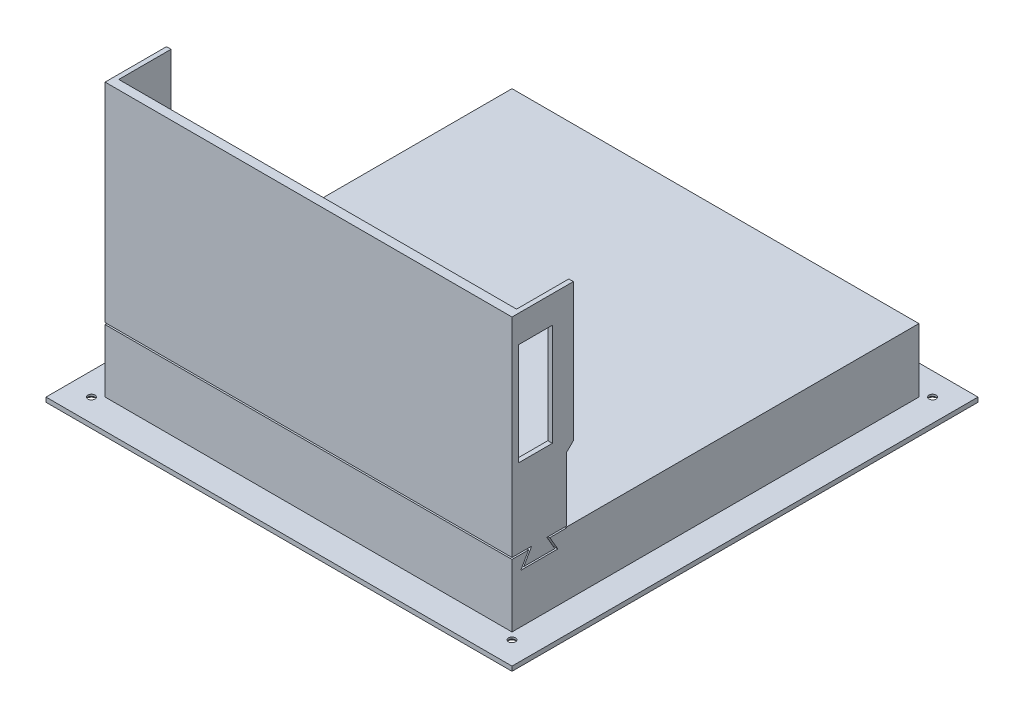
SolidWorks part; units mm, degrees
ref_plane "Front Plane" through (0, 0, 0) normal (0, 0, 1) x (1, 0, 0)
ref_plane "Top Plane" through (0, 0, 0) normal (0, 1, 0) x (1, 0, 0)
ref_plane "Right Plane" through (0, 0, 0) normal (1, 0, 0) x (0, 0, -1)
sketch "Sketch1" plane through (0, 0, 0) normal (0, 1, 0) x (1, 0, 0)
  line L1 (-87.5, 87.5) -> (87.5, 87.5)
  line L2 (-87.5, 87.5) -> (-87.5, -87.5)
  line L3 (-87.5, -87.5) -> (87.5, -87.5)
  line L4 (87.5, 87.5) -> (87.5, -87.5)
  line L5 (-87.5, 87.5) -> (87.5, -87.5) construction
  line L6 (-87.5, -87.5) -> (87.5, 87.5) construction
  point P0 (0, 0)
  dimension "D1" = 175
  dimension "D2" = 175
extrude "Boss-Extrude1" add sketch "Sketch1" along normal blind 2
sketch "Sketch2" plane through (0, 0, 0) normal (0, 1, 0) x (1, 0, 0)
  line L4 (-83, -33.5) -> (-79.25, -33.5)
  line L5 (-71.125, -48.5) -> (-61.125, -48.5)
  line L6 (-82.5, 42.5) -> (-78.75, 42.5)
  line L7 (-82.5, 42.5) -> (-82.5, 30.5)
  line L8 (-82.5, 30.5) -> (-78.75, 30.5)
  line L9 (-78.75, 42.5) -> (-78.75, 30.5)
  line L10 (-82.5, 42.5) -> (-78.75, 30.5) construction
  line L11 (-82.5, 30.5) -> (-78.75, 42.5) construction
  line L12 (87.5, 87.5) -> (-87.5, 87.5) construction
  line L13 (-87.5, 87.5) -> (-87.5, -87.5) construction
  line L14 (-48.7483, 30.5) -> (-52.4983, 30.5)
  line L15 (-48.7483, 42.5) -> (-48.7483, 30.5)
  line L16 (-52.4983, 42.5) -> (-52.4983, 30.5)
  line L17 (-48.7483, 42.5) -> (-52.4983, 42.5)
  line L18 (-44.5, 49) -> (-40.75, 49)
  line L19 (-83, -33.5) -> (-83, -45.5)
  line L20 (-83, -45.5) -> (-79.25, -45.5)
  line L21 (-79.25, -33.5) -> (-79.25, -45.5)
  line L22 (-83, -33.5) -> (-79.25, -45.5) construction
  line L23 (-83, -45.5) -> (-79.25, -33.5) construction
  line L28 (-87.5, -87.5) -> (87.5, -87.5) construction
  line L29 (-53, -33.5) -> (-49.25, -33.5)
  line L30 (-53, -33.5) -> (-53, -45.5)
  line L31 (-53, -45.5) -> (-49.25, -45.5)
  line L32 (-49.25, -33.5) -> (-49.25, -45.5)
  line L33 (-53, -33.5) -> (-49.25, -45.5) construction
  line L34 (-53, -45.5) -> (-49.25, -33.5) construction
  line L35 (-44.5, 49) -> (-44.5, 37)
  line L36 (-44.5, 37) -> (-40.75, 37)
  line L37 (-40.75, 49) -> (-40.75, 37)
  line L38 (-44.5, 49) -> (-40.75, 37) construction
  line L39 (-44.5, 37) -> (-40.75, 49) construction
  line L40 (-14.5, 49) -> (-10.75, 49)
  line L41 (-14.5, 49) -> (-14.5, 37)
  line L42 (-14.5, 37) -> (-10.75, 37)
  line L43 (-10.75, 49) -> (-10.75, 37)
  line L44 (-14.5, 49) -> (-10.75, 37) construction
  line L45 (-14.5, 37) -> (-10.75, 49) construction
  line L46 (-70.6242, 5.5249) -> (-60.6242, 5.5249)
  line L47 (-70.6242, 75.5249) -> (-60.6242, 75.5249)
  line L48 (-70.6242, 75.5249) -> (-70.6242, 67.5249)
  line L49 (-70.6242, 67.5249) -> (-60.6242, 67.5249)
  line L50 (-60.6242, 75.5249) -> (-60.6242, 67.5249)
  line L51 (-70.6242, 75.5249) -> (-60.6242, 67.5249) construction
  line L52 (-70.6242, 67.5249) -> (-60.6242, 75.5249) construction
  line L53 (-70.6242, 5.5249) -> (-70.6242, -2.4751)
  line L54 (-70.6242, -2.4751) -> (-60.6242, -2.4751)
  line L55 (-60.6242, 5.5249) -> (-60.6242, -2.4751)
  line L56 (-70.6242, 5.5249) -> (-60.6242, -2.4751) construction
  line L57 (-70.6242, -2.4751) -> (-60.6242, 5.5249) construction
  line L58 (-71.125, -20.5) -> (-61.125, -20.5)
  line L59 (-71.125, -20.5) -> (-71.125, -28.5)
  line L60 (-71.125, -28.5) -> (-61.125, -28.5)
  line L61 (-61.125, -20.5) -> (-61.125, -28.5)
  line L62 (-71.125, -20.5) -> (-61.125, -28.5) construction
  line L63 (-71.125, -28.5) -> (-61.125, -20.5) construction
  line L64 (-71.125, -48.5) -> (-71.125, -56.5)
  line L65 (-71.125, -56.5) -> (-61.125, -56.5)
  line L66 (-61.125, -48.5) -> (-61.125, -56.5)
  line L67 (-71.125, -48.5) -> (-61.125, -56.5) construction
  line L68 (-71.125, -56.5) -> (-61.125, -48.5) construction
  line L69 (-32.625, 6.5) -> (-22.625, 6.5)
  line L70 (-32.625, 76.5) -> (-22.625, 76.5)
  line L71 (-32.625, 76.5) -> (-32.625, 68.5)
  line L72 (-32.625, 68.5) -> (-22.625, 68.5)
  line L73 (-22.625, 76.5) -> (-22.625, 68.5)
  line L74 (-32.625, 76.5) -> (-22.625, 68.5) construction
  line L75 (-32.625, 68.5) -> (-22.625, 76.5) construction
  line L76 (-32.625, 6.5) -> (-32.625, -1.5)
  line L77 (-32.625, -1.5) -> (-22.625, -1.5)
  line L78 (-22.625, 6.5) -> (-22.625, -1.5)
  line L79 (-32.625, 6.5) -> (-22.625, -1.5) construction
  line L80 (-32.625, -1.5) -> (-22.625, 6.5) construction
  line L87 (4.5, 59.625) -> (12.5, 59.625)
  line L91 (4.5, 59.625) -> (4.5, 49.625)
  line L92 (4.5, 49.625) -> (12.5, 49.625)
  line L93 (12.5, 59.625) -> (12.5, 49.625)
  line L94 (4.5, 59.625) -> (12.5, 49.625) construction
  line L95 (4.5, 49.625) -> (12.5, 59.625) construction
  line L99 (87.5, -87.5) -> (87.5, 87.5) construction
  line L100 (57.5, 59.625) -> (65.5, 59.625)
  line L101 (57.5, 59.625) -> (57.5, 49.625)
  line L106 (57.5, 49.625) -> (65.5, 49.625)
  line L107 (65.5, 59.625) -> (65.5, 49.625)
  line L112 (57.5, 59.625) -> (65.5, 49.625) construction
  line L113 (57.5, 49.625) -> (65.5, 59.625) construction
  line L114 (32.5, 71.5) -> (44.5, 71.5)
  line L115 (32.5, 51.25) -> (44.5, 51.25)
  line L120 (32.5, 71.5) -> (32.5, 67.75)
  line L121 (32.5, 67.75) -> (44.5, 67.75)
  line L122 (32.5, 51.25) -> (32.5, 47.5)
  line L123 (32.5, 47.5) -> (44.5, 47.5)
  line L124 (44.5, 51.25) -> (44.5, 47.5)
  line L125 (32.5, 51.25) -> (44.5, 47.5) construction
  line L126 (32.5, 47.5) -> (44.5, 51.25) construction
  line L127 (44.5, 71.5) -> (44.5, 67.75)
  line L128 (32.5, 71.5) -> (44.5, 67.75) construction
  line L129 (32.5, 67.75) -> (44.5, 71.5) construction
  point P0 (-80.625, 36.5)
  point P5 (-52.4983, 36.5)
  point P6 (-78.75, 36.5)
  point P7 (-80.625, 42.5)
  point P16 (-81.125, -39.5)
  point P17 (-42.625, 43)
  point P19 (-53, -39.5)
  point P25 (8.5, 54.625)
  point P30 (-79.25, -39.5)
  point P31 (-65.6242, 1.5249)
  point P33 (-14.5, 43)
  point P38 (-65.6242, 71.5249)
  point P43 (-40.75, 43)
  point P51 (-27.625, 2.5)
  point P53 (-27.625, 72.5)
  point P55 (-66.125, -24.5)
  point P56 (-66.125, -52.5)
  point P75 (61.5, 54.625)
  point P80 (38.5, 49.375)
  point P85 (38.5, 69.625)
  dimension "D1" = 3.75
  dimension "D2" = 12
  dimension "D3" = 45
  dimension "D4" = 5
  dimension "D5" = 26.2517
  dimension "D6" = 3.75
  dimension "D7" = 12
  dimension "D8" = 3.75
  dimension "D9" = 12
  dimension "D10" = 4.5
  dimension "D11" = 42
  dimension "D12" = 26.25
  dimension "D13" = 26.25
  dimension "D14" = 43
  dimension "D15" = 11
  dimension "D16" = 10
  dimension "D17" = 8
  dimension "D18" = 8.1258
  dimension "D19" = 25.0249
  dimension "D20" = 62
  dimension "D21" = 8
  dimension "D22" = 20
  dimension "D23" = 10
  dimension "D24" = 8.125
  dimension "D25" = 5
  dimension "D26" = 10
  dimension "D27" = 8
  dimension "D28" = 62
  dimension "D29" = 19.5
  dimension "D30" = 8.125
  dimension "D31" = 10
  dimension "D32" = 8
  dimension "D33" = 10
  dimension "D34" = 8
  dimension "D35" = 43
  dimension "D36" = 20
  dimension "D37" = 40
  dimension "D38" = 45
  dimension "D39" = 8.125
  dimension "D40" = 3.75
  dimension "D41" = 12
  dimension "D42" = 16.5
  dimension "D43" = 3.75
  dimension "D44" = 12
extrude "Boss-Extrude13" add sketch "Sketch2" against normal blind 23 contours L87 L93 L92 L91 | L115 L124 L123 L122 | L114 L127 L121 L120 | L100 L107 L106 L101 region at (8.5, 0, -54.625) region at (38.5, 0, -49.375)
extrude "Boss-Extrude14" add sketch "Sketch2<4>" against normal blind 20 contours L5 L66 L65 L64 | L4 L21 L20 L19 | L29 L32 L31 L30 | L58 L61 L60 L59 region at (-81.125, 0, 39.5) region at (-66.125, 0, 52.5) region at (-51.125, 0, 39.5)
sketch "Sketch2<4>" plane through (0, 0, 0) normal (0, 1, 0) x (1, 0, 0) same geometry as "Sketch2"
extrude "Boss-Extrude15" add sketch "Sketch2<5>" against normal blind 22 contours L69 L78 L77 L76 | L35 L36 L37 L18 | L70 L73 L72 L71 | L40 L43 L42 L41 region at (-27.625, 0, -2.5)
sketch "Sketch2<5>" plane through (0, 0, 0) normal (0, 1, 0) x (1, 0, 0) same geometry as "Sketch2"
extrude "Boss-Extrude19" add sketch "Sketch2<7>" against normal blind 22 contours L46 L55 L54 L53 | L17 L15 L14 L16 | L7 L8 L9 L6 | L47 L50 L49 L48 region at (-50.6233, 0, -36.5) region at (-65.6242, 0, -1.5249)
sketch "Sketch2<7>" plane through (0, 0, 0) normal (0, 1, 0) x (1, 0, 0) same geometry as "Sketch2"
extrude "Boss-Extrude20" add sketch "Sketch2<8>" against normal blind 5 contours L70 L73 L72 L71 | L40 L43 L42 L41 | L18 L37 L36 L35 | L78 L77 L76 L69
sketch "Sketch2<8>" plane through (0, 0, 0) normal (0, 1, 0) x (1, 0, 0) same geometry as "Sketch2"
sketch "Sketch11" plane through (0, 0, 0) normal (0, -1, 0) x (1, 0, 0)
  line L0 (19.5, -10.5) -> (-0.5, -10.5)
  line L1 (79.5, -10.5) -> (24.5, -10.5)
  line L2 (79.5, -10.5) -> (79.5, -5.5)
  line L3 (79.5, -5.5) -> (24.5, -5.5)
  line L4 (-0.5, -10.5) -> (-0.5, -5.5)
  line L5 (24.5, -30.5) -> (19.5, -30.5)
  line L6 (24.5, -30.5) -> (24.5, -10.5)
  line L7 (24.5, 1.5) -> (19.5, 1.5)
  line L8 (19.5, -30.5) -> (19.5, -10.5)
  line L9 (19.5, -5.5) -> (19.5, 1.5)
  line L10 (19.5, -5.5) -> (-0.5, -5.5)
  line L12 (87.5, 87.5) -> (87.5, -87.5) construction
  line L13 (87.5, -87.5) -> (-87.5, -87.5) construction
  line L14 (24.5, -5.5) -> (24.5, 1.5)
  dimension "D1" = 5
  dimension "D2" = 5
  dimension "D3" = 8
  dimension "D4" = 57
  dimension "D6" = 20
  dimension "D7" = 55
extrude "Boss-Extrude7" add sketch "Sketch11" along normal blind 33
sketch "Sketch10" plane through (0, 0, 0) normal (0, -1, 0) x (1, 0, 0)
  line L0 (10.5, 35.5) -> (-21.5, 35.5)
  line L1 (72.5, 35.5) -> (17.5, 35.5)
  line L2 (72.5, 35.5) -> (72.5, 45.5)
  line L3 (72.5, 45.5) -> (17.5, 45.5)
  line L4 (-21.5, 35.5) -> (-21.5, 45.5)
  line L5 (17.5, 12.5) -> (10.5, 12.5)
  line L6 (17.5, 12.5) -> (17.5, 35.5)
  line L7 (17.5, 65.5) -> (10.5, 65.5)
  line L8 (10.5, 12.5) -> (10.5, 35.5)
  line L9 (17.5, 45.5) -> (17.5, 65.5)
  line L10 (10.5, 45.5) -> (10.5, 65.5)
  line L11 (10.5, 45.5) -> (-21.5, 45.5)
  line L12 (87.5, 87.5) -> (87.5, -87.5) construction
  line L13 (87.5, -87.5) -> (-87.5, -87.5) construction
  dimension "D1" = 7
  dimension "D2" = 10
  dimension "D3" = 100
  dimension "D4" = 20
  dimension "D6" = 55
  dimension "D7" = 15
  dimension "D8" = 23
extrude "Boss-Extrude6" add sketch "Sketch10" along normal blind 30
sketch "Sketch4" plane through (0, 2, 0) normal (0, -1, 0) x (1, 0, 0)
  line L0 (-87.5, 87.5) -> (87.5, 87.5) construction
  line L1 (-89.5, 89.5) -> (89.5, 89.5)
  line L3 (-87.5, 87.5) -> (87.5, 87.5)
  line L6 (89.5, 89.5) -> (89.5, -89.5)
  line L8 (87.5, 87.5) -> (87.5, -87.5)
  line L10 (-89.5, 89.5) -> (-89.5, -89.5)
  line L12 (-87.5, 87.5) -> (-87.5, -87.5)
  line L13 (-89.5, -89.5) -> (89.5, -89.5)
  line L15 (-87.5, -87.5) -> (87.5, -87.5)
  line L17 (87.5, 87.5) -> (87.5, -87.5) construction
  line L21 (-87.5, -87.5) -> (-87.5, 87.5) construction
  line L22 (87.5, -87.5) -> (-87.5, -87.5) construction
  dimension "D2" = 2
  dimension "D3" = 2
  dimension "D5" = 2
  dimension "D6" = 2
extrude "Boss-Extrude3" add sketch "Sketch4" along normal blind 30
sketch "Sketch5" plane through (0, -28, 0) normal (0, -1, 0) x (1, 0, 0)
  line L1 (-102.5, 102.5) -> (102.5, 102.5)
  line L2 (-102.5, 102.5) -> (-102.5, -102.5)
  line L3 (-102.5, -102.5) -> (102.5, -102.5)
  line L4 (102.5, 102.5) -> (102.5, -102.5)
  line L5 (-102.5, 102.5) -> (102.5, -102.5) construction
  line L6 (-102.5, -102.5) -> (102.5, 102.5) construction
  line L7 (-89.5, 89.5) -> (89.5, 89.5)
  line L8 (-89.5, 89.5) -> (-89.5, -89.5)
  line L9 (-89.5, -89.5) -> (89.5, -89.5)
  line L10 (89.5, 89.5) -> (89.5, -89.5)
  line L11 (-89.5, 89.5) -> (89.5, -89.5) construction
  line L12 (-89.5, -89.5) -> (89.5, 89.5) construction
  point P0 (0, 0)
  point P6 (0, 0)
  dimension "D1" = 205
  dimension "D2" = 205
sketch "Sketch15" plane through (0, 2, 0) normal (0, 1, 0) x (1, 0, 0)
  line L0 (89.5, 89.5) -> (89.5, -89.5) construction
  line L1 (-89.5, -89.5) -> (89.5, -89.5)
  line L2 (-89.5, -89.5) -> (-89.5, -87.5)
  line L3 (-89.5, -87.5) -> (89.5, -87.5)
  line L4 (89.5, -89.5) -> (89.5, -87.5)
  dimension "D1" = 2
extrude "Boss-Extrude9" add sketch "Sketch15" along normal blind 90
sketch "Sketch13" plane through (0, 0, 0) normal (0, -1, 0) x (1, 0, 0)
  line L5 (87.5, 87.5) -> (87.5, -87.5) construction
  line L16 (-87.5, 87.5) -> (87.5, 87.5)
  line L17 (-87.5, 87.5) -> (-87.5, 67.5)
  line L18 (-87.5, 67.5) -> (87.5, 67.5)
  line L19 (87.5, 87.5) -> (87.5, 67.5)
  dimension "D1" = 20
extrude "Cut-Extrude2" cut sketch "Sketch13" against normal up to surface (2 mm away) up to face at (0, 2, -1)
sketch "Sketch17" plane through (0, 0, 87.5) normal (0, 0, -1) x (-1, 0, 0)
  line L12 (0.5, 35) -> (15.5, 35)
  line L14 (15.5, 50) -> (20.5, 50)
  line L16 (20.5, 30) -> (0.5, 30)
  line L17 (0.5, 30) -> (0.5, 35)
  line L19 (-87.5, 35) -> (-62.5, 35)
  line L20 (-62.5, 35) -> (-62.5, 30)
  line L21 (-62.5, 30) -> (-87.5, 30)
  line L22 (-87.5, 30) -> (-87.5, 35)
  line L24 (15.5, 50) -> (15.5, 35)
  line L25 (-89.5, 92) -> (-89.5, 2) construction
  line L29 (13.5, 77.3) -> (18.5, 77.3)
  line L30 (13.5, 77.3) -> (13.5, 90)
  line L31 (13.5, 90) -> (18.5, 90)
  line L32 (18.5, 77.3) -> (18.5, 90)
  line L33 (56.5, 35) -> (56.5, 15)
  line L34 (56.5, 35) -> (20.5, 35)
  line L36 (51.5, 30) -> (20.5, 30)
  line L38 (56.5, 15) -> (87.5, 15)
  line L39 (87.5, 15) -> (87.5, 10)
  line L40 (87.5, 10) -> (51.5, 10)
  line L41 (51.5, 10) -> (51.5, 30)
  line L43 (20.5, 35) -> (20.5, 50)
  line L45 (-89.5, 92) -> (89.5, 92) construction
  line L46 (89.5, 92) -> (89.5, 2) construction
  point P6 (-62.5, 32.5)
  point P26 (0.5, 32.5)
  dimension "D3" = 5
  dimension "D4" = 20
  dimension "D5" = 5
  dimension "D6" = 20
  dimension "D7" = 5
  dimension "D8" = 12.7
  dimension "D10" = 2
  dimension "D11" = 15
  dimension "D12" = 5
  dimension "D13" = 25
  dimension "D14" = 31
  dimension "D15" = 2
  dimension "D16" = 2
  dimension "D17" = 2
  dimension "D18" = 5
  dimension "D19" = 36
  dimension "D20" = 63
  dimension "D21" = 5
  dimension "D22" = 20
  dimension "D23" = 20
  dimension "D24" = 27.3
extrude "Boss-Extrude11" add sketch "Sketch17" along normal blind 5 contours L22 L21 L20 L19 | L16 L43 L14 L24 L12 L17 | L29 L32 L31 L30 | L34 L43 L14 L24 L12 L17 L16 L36 L41 L40 L39 L38 L33 region at (-8, 34.0425, 87.5) region at (75, 32.5, 87.5) region at (-16, 83.65, 87.5)
ref_plane "Plane1" through (87.5, 2, 87.5) normal (0, 0, 1) x (1, 0, 0)
sketch "Sketch24" plane through (89.5, 0, 0) normal (1, 0, 0) x (0, 0, -1)
  line L0 (-65.5, 2) -> (-65.5, 30.4086)
  line L1 (89.5, 2) -> (-87.5, 2) construction
  line L2 (-65.5, 30.4086) -> (-62.5, 33.4086)
  line L3 (-62.5, 33.4086) -> (-62.5, 92)
  line L4 (-62.5, 92) -> (-87.5, 92)
  line L5 (-87.5, 92) -> (-87.5, 2) construction
  line L6 (-87.5, 92) -> (-87.5, 2)
  line L7 (-87.5, 2) -> (-65.5, 2)
  dimension "D1" = 225
  dimension "D2" = 22
  dimension "D3" = 25
  dimension "D4" = 58.5914
extrude "Boss-Extrude16" add sketch "Sketch24" against normal blind 2 separate body
sketch "Sketch26" plane through (-89.5, 0, 0) normal (-1, 0, 0) x (0, 0, 1)
  line L0 (65.5, 2) -> (65.5, 30.4086)
  line L1 (65.5, 30.4086) -> (62.5, 33.4086)
  line L2 (62.5, 33.4086) -> (62.5, 92)
  line L3 (62.5, 92) -> (87.5, 92)
  line L4 (87.5, 92) -> (87.5, 2)
  line L5 (87.5, 2) -> (65.5, 2)
extrude "Boss-Extrude17" add sketch "Sketch26" against normal blind 2
sketch "Sketch27" plane through (-87.5, 0, 0) normal (1, 0, 0) x (0, 0, -1)
  line L0 (-64.5, 34.237) -> (-67.5, 31.237)
  line L1 (-62.5, 92) -> (-64.5, 92)
  line L2 (-62.5, 92) -> (-62.5, 33.4086)
  line L4 (-64.5, 92) -> (-64.5, 34.237)
  line L5 (-67.5, 31.237) -> (-67.5, 2)
  line L6 (-67.5, 2) -> (-65.5, 2)
  line L7 (-65.5, 2) -> (-65.5, 30.4086)
  line L8 (-65.5, 30.4086) -> (-62.5, 33.4086)
  line L9 (-87.5, 2) -> (-65.5, 2) construction
  line L10 (-65.5, 30.4086) -> (-65.5, 2) construction
  dimension "D1" = 2
  dimension "D2" = 2
  dimension "D3" = 2
extrude "Boss-Extrude18" add sketch "Sketch27" along normal up to next
extrude "Boss-Extrude4" add sketch "Sketch5" against normal blind 2
sketch "Sketch8" plane through (0, -28, 0) normal (0, -1, 0) x (-1, 0, 0)
  line L0 (102.5, 102.5) -> (-102.5, 102.5) construction
  line L1 (-102.5, 102.5) -> (-102.5, -102.5) construction
  line L2 (102.5, -102.5) -> (102.5, 102.5) construction
  line L3 (-102.5, -102.5) -> (102.5, -102.5) construction
  point P0 (-92.5, 92.5)
  point P2 (92.5, 92.5)
  point P4 (92.5, -92.5)
  point P6 (-92.5, -92.5)
  dimension "D1" = 10
  dimension "D2" = 10
  dimension "D3" = 10
  dimension "D4" = 10
  dimension "D5" = 10
  dimension "D6" = 10
  dimension "D7" = 10
  dimension "D8" = 10
hole_wizard "CSK for M2.5 Flat Head Machine Screw1" positions "Sketch8" profile "Sketch7" countersink size "M2.5" standard "ANSI Metric" end condition up to next
sketch "Sketch7" plane through (92.5, -28, -92.5) normal (1, 0, 0) x (0, 0, -1)
  line L0 (0, 0) -> (0, 2)
  line L1 (0, 2) -> (1.55, 2)
  line L2 (1.55, 2) -> (1.55, 1.2)
  line L3 (1.55, 1.2) -> (2.75, 0)
  line L5 (2.75, 0) -> (0, 0)
  line L6 (-1.55, 1.2) -> (-2.75, 0) construction
  line L11 (0, -6.35) -> (0, 107.95) construction
  dimension "Thru Hole Dia." = 3.1
  dimension "Thru Hole Depth" = 2
  dimension "Near C'Sink Dia." = 5.5
  dimension "Near C'Sink Angle" = 90
sketch "Sketch21" plane through (0, 92, 0) normal (0, 1, 0) x (1, 0, 0)
  line L21 (89.5, -89.5) -> (89.5, -62.5) construction
  line L25 (-89.5, -89.5) -> (89.5, -89.5)
  line L26 (-89.5, -89.5) -> (-89.5, -85.5)
  line L27 (-87.5, -85.5) -> (87.5, -85.5)
  line L28 (89.5, -89.5) -> (89.5, -85.5)
  line L29 (-89.5, -62.5) -> (-89.5, -89.5) construction
  line L31 (89.5, -62.5) -> (-89.5, -62.5)
  line L32 (89.5, -62.5) -> (89.5, -69.5)
  line L33 (87.5, -66.5) -> (-87.5, -66.5)
  line L34 (-89.5, -62.5) -> (-89.5, -66.5)
  line L36 (-89.5, -85.5) -> (-89.5, -66.5)
  line L38 (-87.5, -85.5) -> (-87.5, -66.5)
  line L41 (89.5, -85.5) -> (89.5, -69.5)
  line L43 (87.5, -85.5) -> (87.5, -66.5)
  line L44 (-89.5, -62.5) -> (89.5, -62.5) construction
  dimension "D1" = 4
  dimension "D2" = 4
extrude "Boss-Extrude12" add sketch "Sketch21" along normal blind 2 contours L28 L25 L26 L36 L34 L31 L32 L41 | L27 L43 L33 L38
sketch "Sketch22" plane through (89.5, 0, 0) normal (1, 0, 0) x (0, 0, -1)
  line L0 (-89.5, -26) -> (-89.5, 94) construction
  line L1 (-71.75, 82) -> (-86.75, 82)
  line L2 (-71.75, 82) -> (-71.75, 37)
  line L3 (-71.75, 37) -> (-86.75, 37)
  line L4 (-86.75, 82) -> (-86.75, 37)
  line L6 (-89.5, 94) -> (-62.5, 94) construction
  dimension "D1" = 2.75
  dimension "D2" = 45
  dimension "D3" = 12
  dimension "D4" = 15
extrude "Cut-Extrude3" cut sketch "Sketch22" against normal up to next
sketch "Sketch28" plane through (89.5, 0, 0) normal (1, 0, 0) x (0, 0, -1)
  line L0 (-65.5, 2) -> (-73.5, 2)
  line L1 (-65.5, 2) -> (-65.5, 30.4086) construction
  line L2 (89.5, 2) -> (-65.5, 2) construction
  line L3 (-73.5, 2) -> (-70, -4.0622)
  line L4 (-70, -4.0622) -> (-85, -4.0622)
  line L5 (-85, -4.0622) -> (-81.5, 2)
  line L6 (-81.5, 2) -> (-89.5, 2)
  line L7 (-89.5, -26) -> (-89.5, 94) construction
  point P6 (-77.5, -4.0622)
  dimension "D1" = 60
  dimension "D2" = 60
  dimension "D3" = 12
  dimension "D4" = 15
  dimension "D5" = 8
  dimension "D6" = 8
extrude "Cut-Extrude-Thin1" cut sketch "Sketch28" against normal through all thin thin type mid plane wall 0.75
chamfer "Chamfer1" distance 5 angle 45 1 edges at (-69.5, 10, 87.5)
chamfer "Chamfer2" distance 5 angle 45 1 edges at (-26, 30, 87.5)
chamfer "Chamfer3" distance 5 angle 45 2 edges at (75, 30, 87.5) (-16, 77.3, 87.5)
chamfer "Chamfer4" distance 2 angle 45 2 edges at (0, 92, 87.5) (0, 92, 64.5)
sketch "Sketch29" plane through (0, 0, 62.5) normal (0, 0, -1) x (-1, 0, 0)
  line L0 (89.5, 2) -> (-89.5, 2) construction
  line L1 (-87.5, 94) -> (87.5, 94)
  line L2 (-87.5, 94) -> (-87.5, 2)
  line L3 (-87.5, 2) -> (87.5, 2)
  line L4 (87.5, 94) -> (87.5, 2)
  line L5 (87.5, 90) -> (87.5, 34.237) construction
  line L6 (-87.5, 82) -> (-87.5, 37) construction
  point P9 (0, 0)
extrude "Cut-Extrude4" cut sketch "Sketch29" against normal up to surface (5 mm away) up to face at (0, 0.8125, 67.5)
